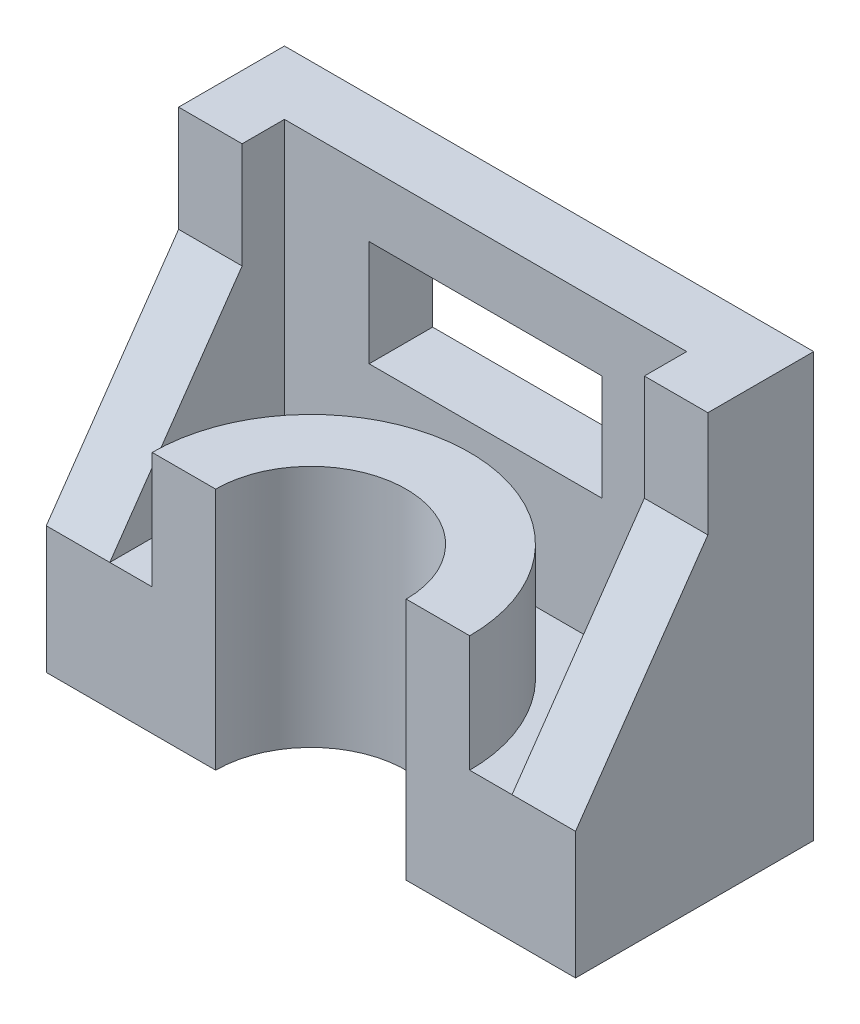
SolidWorks part; units mm, degrees
ref_plane "Front Plane" through (0, 0, 0) normal (0, 0, 1) x (1, 0, 0)
ref_plane "Top Plane" through (0, 0, 0) normal (0, 1, 0) x (1, 0, 0)
ref_plane "Right Plane" through (0, 0, 0) normal (1, 0, 0) x (0, 0, -1)
sketch "Sketch1" plane through (0, 0, 0) normal (0, 1, 0) x (1, 0, 0)
  line L0 (-62.2149, -16.3055) -> (-50.2149, -16.3055)
  line L1 (-62.2149, 28.6945) -> (37.7851, 28.6945)
  line L2 (-62.2149, 28.6945) -> (-62.2149, -16.3055)
  line L3 (-62.2149, -16.3055) -> (-30.2149, -16.3055)
  line L4 (37.7851, 28.6945) -> (37.7851, -16.3055)
  line L5 (-50.2149, -16.3055) -> (-50.2149, 8.6945)
  line L6 (-50.2149, 8.6945) -> (-62.2149, 8.6945)
  line L7 (-50.2149, 8.6945) -> (-50.2149, 16.6945)
  line L8 (-50.2149, 16.6945) -> (25.7851, 16.6945)
  line L9 (25.7851, 16.6945) -> (25.7851, 8.6945)
  line L10 (25.7851, 8.6945) -> (37.7851, 8.6945)
  line L11 (25.7851, 8.6945) -> (25.7851, -16.3055)
  line L12 (5.7851, -16.3055) -> (37.7851, -16.3055)
  arc A1 (17.7851, -16.3055) -> (-42.2149, -16.3055) centre (-12.2149, -16.3055) ccw
  arc A2 (5.7851, -16.3055) -> (-30.2149, -16.3055) centre (-12.2149, -16.3055) ccw
extrude "Boss-Extrude1" add sketch "Sketch1" along normal blind 24 contours A1 L12 L11 L9 L8 L7 L5 L3 region at (-49.3863, 0, 3.8055)
extrude "Boss-Extrude3" add sketch "Sketch1<4>" along normal blind 60 contours L5 L6 L2 L0 | L11 L12 L4 L10 region at (-56.2149, 0, 3.8055) region at (31.7851, 0, 3.8055)
sketch "Sketch1<4>" plane through (0, 0, 0) normal (0, 1, 0) x (1, 0, 0) same geometry as "Sketch1"
extrude "Boss-Extrude5" add sketch "Sketch1<7>" along normal blind 80 contours L9 L10 L4 L1 L2 L6 L7 L8 region at (-12.2149, 0, -21.3152)
sketch "Sketch1<7>" plane through (0, 0, 0) normal (0, 1, 0) x (1, 0, 0) same geometry as "Sketch1"
sketch "Sketch3" plane through (-62.2149, 0, 0) normal (-1, 0, 0) x (0, 0, 1)
  line L1 (16.3055, 60) -> (16.3055, 0) construction
  line L2 (16.3055, 24) -> (-8.6945, 60)
  line L3 (-8.6945, 60) -> (16.3055, 60)
  line L4 (-8.6945, 60) -> (16.3055, 60) construction
  line L5 (16.3055, 60) -> (16.3055, 24)
extrude "Cut-Extrude4" cut sketch "Sketch3" against normal blind 104
extrude "Boss-Extrude6" add sketch "Sketch1<8>" along normal blind 46 contours A2 L12 A1 L3 region at (-12.2149, 0, -13.0237)
sketch "Sketch1<8>" plane through (0, 0, 0) normal (0, 1, 0) x (1, 0, 0) same geometry as "Sketch1"
sketch "Sketch5" plane through (0, 0, -16.6945) normal (0, 0, 1) x (1, 0, 0)
  line L0 (-50.2149, 80) -> (-50.2149, 24) construction
  line L1 (-34.2149, 68) -> (9.7851, 68)
  line L2 (-34.2149, 68) -> (-34.2149, 48)
  line L3 (-34.2149, 48) -> (9.7851, 48)
  line L4 (9.7851, 68) -> (9.7851, 48)
  line L5 (25.7851, 80) -> (25.7851, 60) construction
  line L6 (-50.2149, 80) -> (25.7851, 80) construction
  dimension "D1" = 16
  dimension "D2" = 16
  dimension "D3" = 20
  dimension "D4" = 12
extrude "Cut-Extrude5" cut sketch "Sketch5" against normal blind 46
